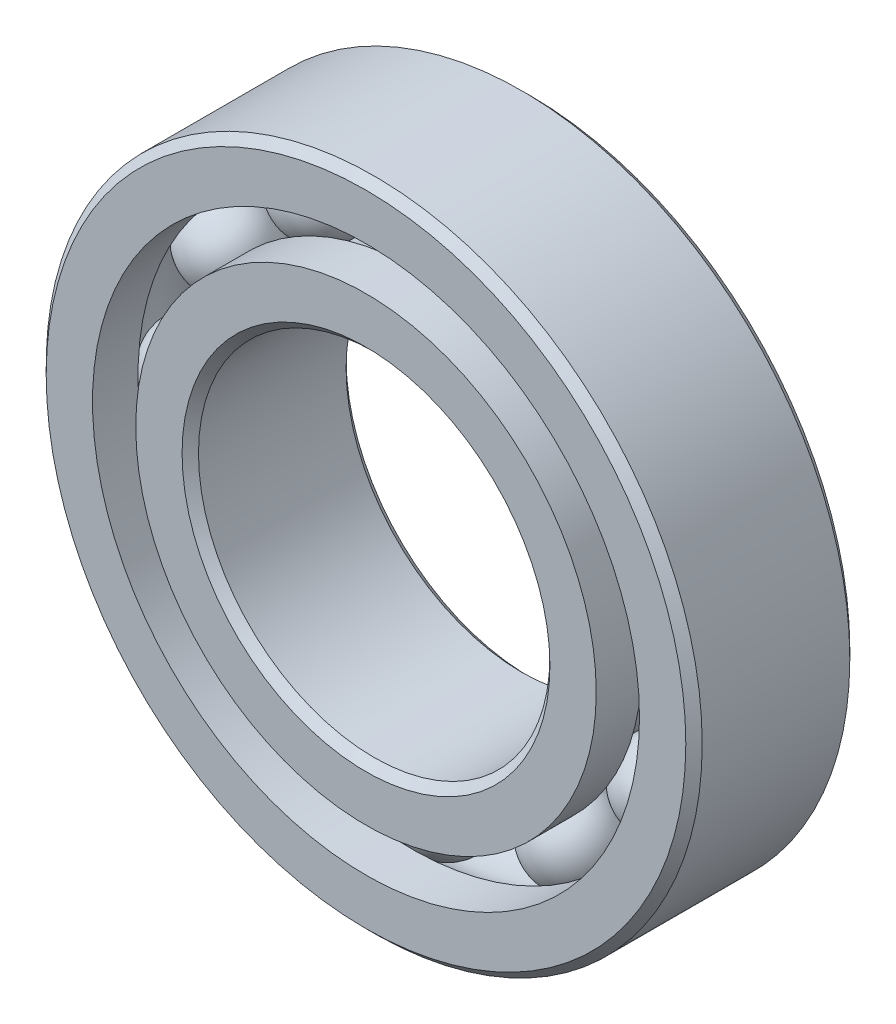
SolidWorks part; units mm, degrees
ref_plane "Front Plane" through (0, 0, 0) normal (0, 0, 1) x (1, 0, 0)
ref_plane "Top Plane" through (0, 0, 0) normal (0, 1, 0) x (1, 0, 0)
ref_plane "Right Plane" through (0, 0, 0) normal (1, 0, 0) x (0, 0, -1)
sketch "Sketch1" plane through (0, 0, 0) normal (1, 0, 0) x (0, 0, -1)
  line L0 (-3.5, 0) -> (3.5, 0) construction
  line L1 (0, 14) -> (0, -14) construction
  line L2 (3.15, 14) -> (-3.15, 14)
  line L3 (-3.15, 14) -> (-3.5, 13.65)
  line L4 (-3.5, 13.65) -> (-3.5, 11.6731)
  line L5 (-3.5, 11.6731) -> (-1.5556, 11.6731)
  line L6 (3.5, 11.6731) -> (1.5556, 11.6731)
  line L7 (3.5, 13.65) -> (3.5, 11.6731)
  line L8 (3.15, 14) -> (3.5, 13.65)
  line L9 (0, 14) -> (0, 10.75) construction
  line L10 (0, 10.75) -> (0, 7.5) construction
  arc A0 (-1.5556, 11.6731) -> (1.5556, 11.6731) centre (0, 10.75) cw
  point P14 (0, 7.5)
  dimension "Width" = 7
  dimension "OD" = 28
  dimension "D1" = 45
  dimension "D2" = 0.35
  dimension "Shaft Dia" = 15
  dimension "D3" = 3.1111
  dimension "D4" = 0.9231
revolve "Revolve1" add sketch "Sketch1" angle 360 about L0
sketch "Sketch3" plane through (0, 0, 0) normal (1, 0, 0) x (0, 0, -1)
  line L0 (-3.5, 9.8269) -> (-1.5556, 9.8269)
  line L1 (0, 14) -> (0, -14) construction
  line L2 (-3.5, 13.65) -> (-3.5, 11.6731) construction
  line L3 (-3.5, 9.8269) -> (-3.5, 7.85)
  line L4 (-3.15, 14) -> (-3.5, 13.65) construction
  line L5 (-3.5, 7.85) -> (-3.15, 7.5)
  line L6 (-3.15, 7.5) -> (3.15, 7.5)
  line L7 (3.15, 14) -> (3.15, -14) construction
  line L8 (3.15, 7.5) -> (3.5, 7.85)
  line L9 (3.5, -13.65) -> (3.5, 13.65) construction
  line L10 (3.5, 7.85) -> (3.5, 9.8269)
  line L11 (3.5, 9.8269) -> (1.5556, 9.8269)
  line L13 (3.15, 14) -> (3.5, 13.65) construction
  arc A0 (1.5556, 11.6731) -> (-1.5556, 11.6731) centre (0, 10.75) ccw construction
  arc A1 (1.5556, 9.8269) -> (-1.5556, 9.8269) centre (0, 10.75) cw
revolve "Revolve3" add sketch "Sketch3" angle 360 about L0
sketch "Sketch4" plane through (0, 0, 0) normal (1, 0, 0) x (0, 0, -1)
  line L0 (-1.8088, 10.75) -> (1.8088, 10.75)
  arc A2 (-1.8088, 10.75) -> (1.8088, 10.75) centre (0, 10.75) cw
  arc A3 (1.5556, 11.6731) -> (-1.5556, 11.6731) centre (0, 10.75) ccw construction
revolve "Revolve4" add sketch "Sketch4" angle 360 about L0
ref_axis "Axis1" through (0, 0, -3.5) along (0, 0, 1)
pattern_circular "CirPattern1" count 12 every 30 about axis through (0, 0, -3.5) along (0, 0, 1) of bodies 104
sketch "Sketch5" plane through (0, 0, 0) normal (1, 0, 0) x (0, 0, -1)
  line L0 (-3.5, 11.6731) -> (-1.5556, 11.6731) construction
  line L1 (-3.325, 11.6731) -> (-1.8088, 11.6731)
  line L2 (-3.325, 11.6731) -> (-3.325, 9.8269)
  line L3 (-3.325, 9.8269) -> (-1.8088, 9.8269)
  line L4 (-1.8088, 11.6731) -> (-1.8088, 9.8269)
  line L5 (-3.5, 9.8269) -> (-1.5556, 9.8269) construction
  line L6 (3.5, 11.6731) -> (1.5556, 11.6731) construction
  line L7 (3.325, 11.6731) -> (1.8088, 11.6731)
  line L8 (3.325, 11.6731) -> (3.325, 9.8269)
  line L9 (3.325, 9.8269) -> (1.8088, 9.8269)
  line L10 (1.8088, 11.6731) -> (1.8088, 9.8269)
  line L11 (3.5, 9.8269) -> (1.5556, 9.8269) construction
  line L12 (-3.15, 14) -> (-3.5, 13.65) construction
  point P18 (-3.325, 13.825)
equation "\"D2@Sketch1\" = \"Width@Sketch1\"*.05"
equation "\"D3@Sketch1\" = \"Width@Sketch1\"/2.25"
equation "\"D4@Sketch1\" = (((\"OD@Sketch1\"-\"Width@Sketch1\")/2)/3.25)/3.5"
equation "\"D2@CirPattern1\" = 360/\"Balls@CirPattern1\""
